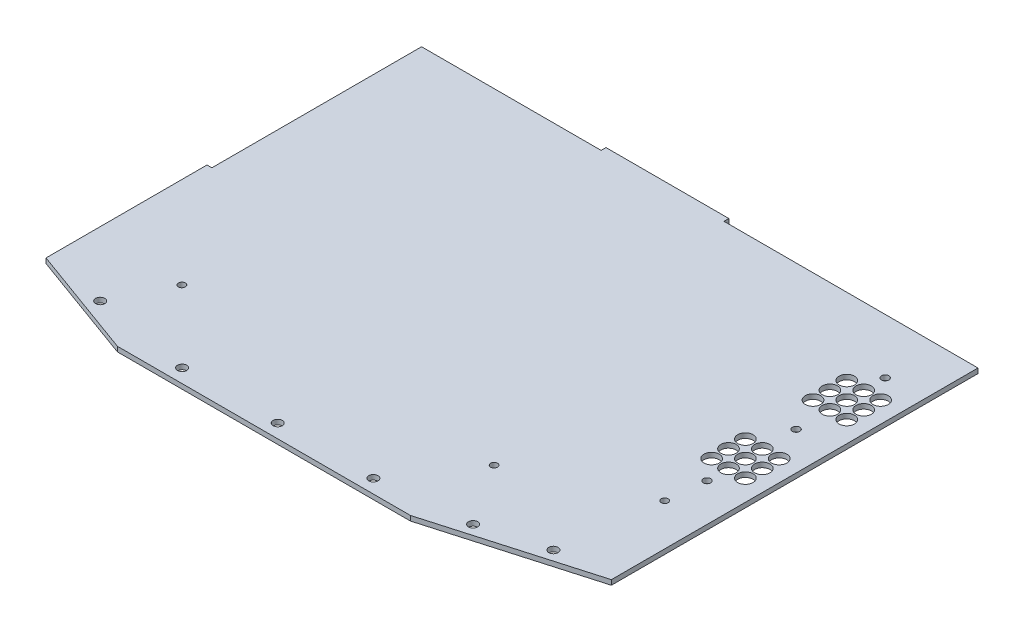
SolidWorks part; units mm, degrees
material "6061-T6 (SS)"
ref_plane "X-Y Datum" through (0, 0, 0) normal (0, 0, 1) x (1, 0, 0)
ref_plane "X-Z Datum" through (0, 0, 0) normal (0, 1, 0) x (1, 0, 0)
ref_plane "Y-Z Datum" through (0, 0, 0) normal (1, 0, 0) x (0, 0, -1)
sketch "Sketch1" plane through (0, 0, 0) normal (0, 0, 1) x (1, 0, 0)
  line L1 (-154.0556, -1.5875) -> (154.0556, -1.5875)
  line L2 (-154.0556, -1.5875) -> (-154.0556, 1.5875)
  line L3 (-154.0556, 1.5875) -> (154.0556, 1.5875)
  line L4 (154.0556, -1.5875) -> (154.0556, 1.5875)
  line L5 (-154.0556, -1.5875) -> (154.0556, 1.5875) construction
  line L6 (-154.0556, 1.5875) -> (154.0556, -1.5875) construction
  point P0 (0, 0)
  dimension "D1" = 3.175
  dimension "D2" = 308.1112
extrude "Boss-Extrude1" add sketch "Sketch1" along normal blind 267.83
sketch "Sketch3" plane through (154.0556, 0, 0) normal (1, 0, 0) x (0, 0, -1)
  line L9 (0, -1.5875) -> (0, 1.5875)
  line L10 (0, 1.5875) -> (-267.83, 1.5875)
  line L11 (-267.83, 1.5875) -> (-267.83, -1.5875)
  line L12 (-267.83, -1.5875) -> (0, -1.5875)
  line L13 (0, -1.5875) -> (0, 1.5875)
  line L14 (0, 1.5875) -> (-267.83, 1.5875)
  line L15 (-267.83, 1.5875) -> (-267.83, -1.5875)
  line L16 (-267.83, -1.5875) -> (0, -1.5875)
  dimension "D1" = 0
extrude "Boss-Extrude3" add sketch "Sketch3" along normal blind 3.175
sketch "Sketch4" plane through (0, 0, 267.83) normal (0, 0, 1) x (1, 0, 0)
  line L1 (157.2306, -1.5875) -> (208.1043, -1.5875)
  line L2 (157.2306, -1.5875) -> (157.2306, 1.5875)
  line L3 (157.2306, 1.5875) -> (208.1043, 1.5875)
  line L4 (208.1043, -1.5875) -> (208.1043, 1.5875)
  dimension "D1" = 3.175
  dimension "D2" = 50.8737
extrude "Boss-Extrude4" add sketch "Sketch4" against normal blind 267.83
sketch "Sketch6" plane through (0, 1.5875, 0) normal (0, 1, 0) x (1, 0, 0)
  line L0 (106.5043, -267.83) -> (106.5043, -223.38)
  line L1 (208.1043, -267.83) -> (-154.0556, -267.83) construction
  line L2 (208.1043, -223.38) -> (106.5043, -223.38)
  line L3 (208.1043, 0) -> (208.1043, -267.83) construction
  line L5 (106.5043, -267.83) -> (208.1047, -238.62)
  line L6 (208.1043, -223.38) -> (208.1047, -238.62)
  line M9 (-154.0556, -267.83) -> (208.1043, -267.83)
  line M10 (208.1043, -267.83) -> (208.1043, 0)
  dimension "D1" = 44.45
  dimension "D2" = 101.6
  dimension "D3" = 15.24
extrude "Cut-Extrude1" cut sketch "Sketch6" against normal through all contours L5 M9 M10 region at (174.2376, 1.5875, 258.0934)
sketch "Sketch11" plane through (0, -1.5875, 0) normal (0, -1, 0) x (1, 0, 0)
  line L0 (-84.2056, 267.83) -> (-84.2056, 242.43)
  line L1 (-154.0556, 267.83) -> (106.5043, 267.83) construction
  line L2 (-154.0556, 242.43) -> (-84.2056, 242.43)
  line L3 (-154.0556, 267.83) -> (-154.0556, 0) construction
  line L4 (-154.0556, 242.43) -> (-84.2056, 267.83)
  line M4 (-154.0556, 267.83) -> (-154.0556, 0)
  line M18 (106.5043, 267.83) -> (-154.0556, 267.83)
  dimension "D1" = 69.85
  dimension "D2" = 25.4
extrude "Cut-Extrude3" cut sketch "Sketch11" against normal through all contours L4 M4 M18 region at (-130.7723, -1.5875, 259.3633)
sketch "Sketch17" plane through (-154.0556, 0, 0) normal (-1, 0, 0) x (0, 0, 1)
  line L0 (136.4994, 1.5875) -> (136.4994, -1.5875)
  line L5 (242.43, 1.5875) -> (136.4994, 1.5875)
  line L9 (242.43, -1.5875) -> (0, -1.5875) construction
  line L10 (136.4994, -1.5875) -> (242.43, -1.5875)
  line L11 (242.43, -1.5875) -> (242.43, 1.5875)
extrude "Boss-Extrude5" add sketch "Sketch17" along normal blind 3.175
sketch "Sketch23" plane through (0, 1.5875, 0) normal (0, 1, 0) x (1, 0, 0)
  line L0 (-154.0556, -242.43) -> (-157.2306, -241.2755)
  line L1 (-157.2306, -242.43) -> (-157.2306, -136.4994) construction
  line L2 (-154.0556, -242.43) -> (-84.2056, -267.83) construction
  line L3 (-154.0556, -242.43) -> (-84.2056, -267.83) construction
extrude "Cut-Extrude7" cut sketch "Sketch23" against normal through all and the other way through all
sketch "Sketch25" plane through (0, -1.5875, 0) normal (0, -1, 0) x (1, 0, 0)
  line L0 (-157.2306, 241.2755) -> (-83.9957, 267.9063) construction
  line L1 (-50.9757, 267.83) -> (-50.9757, 258.94)
  line L2 (-157.2306, 241.2755) -> (-84.2056, 267.83) construction
  line L3 (-118.0827, 255.5111) -> (-115.3206, 247.9154)
  line L4 (-157.2306, 136.4994) -> (-157.2306, 241.2755) construction
  line L5 (-84.2056, 267.83) -> (106.5043, 267.83) construction
  line L6 (-50.9757, 258.94) -> (11.2543, 258.94) construction
  line L7 (11.2543, 258.94) -> (73.4843, 258.94) construction
  line L8 (172.5443, 248.8436) -> (172.5443, 240.7613)
  line L9 (106.5043, 267.83) -> (208.1043, 238.6201) construction
  line L10 (172.5443, 240.7613) -> (131.9043, 252.4453) construction
  circle A0 centre (-115.3206, 247.9154) radius 3
  circle A1 centre (-50.9757, 258.94) radius 3
  circle A2 centre (11.2543, 258.94) radius 3
  circle A3 centre (73.4843, 258.94) radius 3
  circle A4 centre (172.5443, 240.7613) radius 3
  circle A5 centre (131.9043, 252.4453) radius 3
  dimension "D2" = 90
  dimension "D3" = 6
  dimension "D13" = 8.89
  dimension "D1" = 8.0823
  dimension "D4" = 41.91
  dimension "D5" = 33.02
  dimension "D6" = 62.23
  dimension "D7" = 62.23
  dimension "D8" = 33.02
  dimension "D9" = 35.56
  dimension "D10" = 73.96
  dimension "D11" = 40.64
  dimension "D12" = 8.0823
extrude "Cut-Extrude8" cut sketch "Sketch25" against normal blind 3.175 contours A0 | A1 | A2 | A5 | A4 | A3 region at (-116.993, -1.5875, 245.5277) region at (-53.0371, -1.5875, 256.8787) region at (11.2543, -1.5875, 258.94) region at (170.4829, -1.5875, 238.7) region at (131.9043, -1.5875, 252.4453)
sketch "Sketch27" plane through (0, -1.5875, 0) normal (0, -1, 0) x (1, 0, 0)
  circle A0 centre (172.4867, 137.7748) radius 5 construction
  circle A1 centre (172.4867, 137.7748) radius 5
  circle A2 centre (183.4867, 137.7748) radius 5 construction
  circle A3 centre (183.4867, 137.7748) radius 5
  circle A4 centre (194.4867, 137.7748) radius 5 construction
  circle A5 centre (194.4867, 126.7748) radius 5 construction
  circle A6 centre (194.4867, 115.7748) radius 5 construction
  circle A7 centre (183.4867, 126.7748) radius 5 construction
  circle A8 centre (183.4867, 115.7748) radius 5 construction
  circle A9 centre (172.4867, 115.7748) radius 5 construction
  circle A10 centre (172.4867, 126.7748) radius 5 construction
  circle A11 centre (194.4867, 137.7748) radius 5
  circle A12 centre (194.4867, 126.7748) radius 5
  circle A13 centre (194.4867, 115.7748) radius 5
  circle A14 centre (183.4867, 126.7748) radius 5
  circle A15 centre (183.4867, 115.7748) radius 5
  circle A16 centre (172.4867, 115.7748) radius 5
  circle A17 centre (172.4867, 126.7748) radius 5
  circle A18 centre (194.4867, 71.7748) radius 5 construction
  circle A19 centre (194.4867, 60.7748) radius 5 construction
  circle A20 centre (194.4867, 49.7748) radius 5 construction
  circle A21 centre (183.4867, 71.7748) radius 5 construction
  circle A22 centre (183.4867, 60.7748) radius 5 construction
  circle A23 centre (183.4867, 49.7748) radius 5 construction
  circle A24 centre (172.4867, 49.7748) radius 5 construction
  circle A25 centre (172.4867, 60.7748) radius 5 construction
  circle A26 centre (172.4867, 71.7748) radius 5 construction
  circle A27 centre (194.4867, 71.7748) radius 5
  circle A28 centre (194.4867, 60.7748) radius 5
  circle A29 centre (194.4867, 49.7748) radius 5
  circle A30 centre (183.4867, 71.7748) radius 5
  circle A31 centre (183.4867, 60.7748) radius 5
  circle A32 centre (183.4867, 49.7748) radius 5
  circle A33 centre (172.4867, 49.7748) radius 5
  circle A34 centre (172.4867, 60.7748) radius 5
  circle A35 centre (172.4867, 71.7748) radius 5
extrude "Cut-Extrude9" cut sketch "Sketch27" against normal through all
sketch "Sketch28" plane through (0, -1.5875, 0) normal (0, -1, 0) x (1, 0, 0)
  point P1 (105.429, 212.285)
  point P3 (-97.7709, 212.285)
  point P10 (180.965, 176.776)
hole_wizard "M4 Clearance Hole1" positions "Sketch28" profile "Sketch29" hole size "M4" standard "ANSI Metric" end condition through all
sketch "Sketch29" plane through (105.429, -1.5875, 212.285) normal (1, 0, 0) x (0, 0, -1)
  line L0 (0, 0) -> (0, 3.175)
  line L1 (0, 3.175) -> (2.25, 3.175)
  line L2 (2.25, 3.175) -> (2.25, 0)
  line L5 (2.25, 0) -> (0, 0)
  line L11 (0, -6.35) -> (0, 107.95) construction
  dimension "Thru Hole Dia." = 4.5
  dimension "Thru Hole Depth" = 3.175
sketch "Sketch30" plane through (0, 0, 0) normal (0, 0, -1) x (-1, 0, 0)
  line L0 (37.216, 1.5875) -> (37.216, -1.5875) construction
  line L1 (-42.784, 1.5875) -> (37.216, 1.5875) construction
  line L2 (-42.784, 1.5875) -> (-42.784, -1.5875) construction
  line L3 (37.216, 1.5875) -> (37.216, -1.5875)
  line L4 (-42.784, 1.5875) -> (37.216, 1.5875)
  line L5 (-42.784, 1.5875) -> (-42.784, -1.5875)
  line L6 (154.0556, -1.5875) -> (-208.1043, -1.5875) construction
  line L7 (154.0556, -1.5875) -> (-208.1043, -1.5875)
  line M1 (154.0556, 1.5875) -> (-208.1043, 1.5875)
  line M3 (-208.1043, -1.5875) -> (154.0556, -1.5875)
extrude "Boss-Extrude6" add sketch "Sketch30" along normal blind 3.175 contours L5 L3 M1 M3 region at (2.784, 0, 0)
sketch "Sketch31" plane through (0, -1.5875, 0) normal (0, -1, 0) x (1, 0, 0)
  circle A0 centre (183.4867, 151.7748) radius 2.4 construction
  circle A1 centre (183.4867, 151.7748) radius 2.4
extrude "Cut-Extrude10" cut sketch "Sketch31" against normal through all both and the other way through all
pattern_linear "LPattern1" count 3 spacing 58 along (0, 0, -1) of "Cut-Extrude10"
